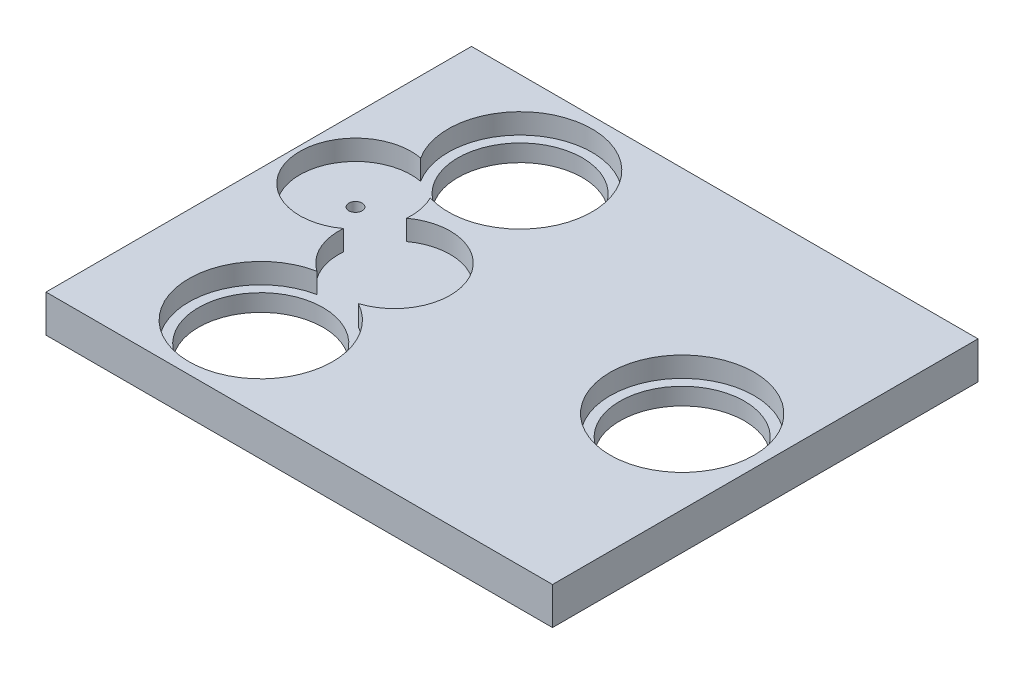
SolidWorks part; units mm, degrees
ref_plane "Front" through (0, 0, 0) normal (0, 0, 1) x (1, 0, 0)
ref_plane "Top" through (0, 0, 0) normal (0, 1, 0) x (1, 0, 0)
ref_plane "Right" through (0, 0, 0) normal (1, 0, 0) x (0, 0, -1)
sketch "Sketch1" plane through (0, 0, 0) normal (0, 1, 0) x (1, 0, 0)
  line L1 (-62.5, -52.5) -> (62.5, -52.5)
  line L2 (-62.5, -52.5) -> (-62.5, 52.5)
  line L3 (-62.5, 52.5) -> (62.5, 52.5)
  line L4 (62.5, -52.5) -> (62.5, 52.5)
  line L5 (-62.5, -52.5) -> (62.5, 52.5) construction
  line L6 (-62.5, 52.5) -> (62.5, -52.5) construction
  point P0 (0, 0)
  dimension "D1" = 125
  dimension "D2" = 105
extrude "Test_Base_Postion" add sketch "Sketch1" along normal blind 9.215
sketch "Thumb_Position" plane through (0, 9.215, 0) normal (0, 1, 0) x (1, 0, 0)
  line L0 (62.5, -52.5) -> (62.5, 52.5) construction
  line L1 (49, -12) -> (17, -12)
  line L2 (49, -12) -> (49, 43)
  line L3 (49, 43) -> (17, 43)
  line L4 (17, -12) -> (17, 43)
  line L5 (33, 43) -> (33, -12) construction
  line L6 (51, -12) -> (15, -12)
  line L7 (51, -12) -> (51, 12)
  line L8 (51, 12) -> (15, 12)
  line L9 (15, -12) -> (15, 12)
  line L10 (33, 12) -> (33, -12) construction
  line L12 (51, 0) -> (15, 0) construction
  circle A1 centre (42, 0) radius 9
  circle A2 centre (42, 0) radius 17.75 construction
  dimension "D6" = 18
  dimension "D7" = 20.5
  dimension "D5" = 35.5
  dimension "D1" = 55
  dimension "D2" = 32
  dimension "D3" = 36
  dimension "D4" = 24
sketch "Finger_Gears_Position" plane through (0, 0, 0) normal (0, -1, 0) x (1, 0, 0)
  line L0 (-30, 32) -> (-30, 49.5) construction
  line L1 (-30, 32) -> (-47.5, 32) construction
  line L2 (-30, -32) -> (-30, -49.5) construction
  line L3 (-30, -32) -> (-47.5, -32) construction
  line L4 (-62.5, -52.5) -> (-62.5, 52.5) construction
  line L5 (-62.5, 52.5) -> (62.5, 52.5) construction
  line L8 (62.5, -52.5) -> (-62.5, -52.5) construction
  line L9 (-62.5, 0) -> (62.5, 0) construction
  line L10 (62.5, 52.5) -> (62.5, -52.5) construction
  line L13 (-30, -32) -> (-43, -32) construction
  line L15 (-43, -48) -> (12, -48) construction
  line L16 (-43, -48) -> (-43, -16) construction
  line L17 (-43, -16) -> (12, -16) construction
  line L18 (12, -48) -> (12, -16) construction
  line L20 (-30, 32) -> (-43, 32) construction
  line L21 (12, -32) -> (-23, -32) construction
  line L22 (-43, 16) -> (12, 16) construction
  line L23 (-43, 16) -> (-43, 48) construction
  line L24 (-43, 48) -> (12, 48) construction
  line L25 (12, 16) -> (12, 48) construction
  line L26 (12, 32) -> (-23, 32) construction
  line L27 (-23, -32) -> (-23, 32) construction
  circle A0 centre (-30, 32) radius 17.5 construction
  circle A1 centre (-30, -32) radius 17.5 construction
  dimension "D1" = 35
  dimension "D2" = 15
  dimension "D3" = 3
  dimension "D4" = 3
  dimension "D5" = 13
  dimension "D6" = 55
  dimension "D7" = 32
  dimension "D8" = 13
  dimension "D9" = 55
  dimension "D10" = 32
  dimension "D11" = 35
  dimension "D12" = 35
sketch "Fingers_Position" plane through (0, 9.215, 0) normal (0, 1, 0) x (1, 0, 0)
  line L0 (12, 32) -> (-23, 32) construction
  line L1 (12, 16) -> (-43, 16)
  line L2 (12, 16) -> (12, 48)
  line L3 (12, 48) -> (-43, 48)
  line L4 (-43, 16) -> (-43, 48)
  line L5 (12, -48) -> (-43, -48)
  line L6 (12, -48) -> (12, -16)
  line L7 (12, -16) -> (-43, -16)
  line L8 (-43, -48) -> (-43, -16)
  line L9 (-23, 32) -> (-23, -32) construction
  line L10 (-23, -32) -> (12, -32) construction
sketch "Thumb_Knuckle_Mount_Position" plane through (0, 0, 0) normal (0, -1, 0) x (1, 0, 0)
  circle A0 centre (42, 0) radius 17.75
  dimension "D1" = 35.5
sketch "Gears_Position" plane through (0, 0, 0) normal (0, -1, 0) x (-1, 0, 0)
  line L0 (30, 32) -> (30, 13.5) construction
  line L1 (30, 32) -> (30.5905, 16.5113) construction
  line L2 (30.7851, 15.5187) -> (29.2149, 15.5187) construction
  line L3 (31.4977, 13.5607) -> (30, 17.6757) construction
  line L4 (28.2415, 13.5838) -> (30, 32) construction
  line L5 (29.2149, 15.5187) -> (27.6518, 15.6679) construction
  line L6 (30, -32) -> (30, -50.5) construction
  line L7 (30.7851, -48.4813) -> (29.2149, -48.4813) construction
  line L8 (30.5905, -47.4887) -> (30, -32) construction
  line L9 (31.4977, -50.4393) -> (30, -46.3243) construction
  line L10 (30, -32) -> (28.2415, -50.4162) construction
  line L11 (29.2149, -48.4813) -> (27.6518, -48.3321) construction
  line L12 (47.5, 8.8753) -> (47.5, -5.6247) construction
  line L13 (47.5, 8.8753) -> (48.0842, -2.6098) construction
  line L14 (48.2849, -3.6) -> (46.7151, -3.6) construction
  line L15 (48.9937, -5.5475) -> (47.5, -1.4436) construction
  line L16 (47.5, 8.8753) -> (45.6827, -5.5103) construction
  line L17 (46.7151, -3.6) -> (45.1577, -3.4033) construction
  line L18 (26.4633, -15.7991) -> (24.8935, -15.7991) construction
  line L19 (25.6784, -3.3238) -> (23.8611, -17.7095) construction
  line L20 (24.8935, -15.7991) -> (23.3362, -15.6024) construction
  line L21 (25.6784, -3.3238) -> (25.6784, -17.8238) construction
  line L22 (25.6784, -3.3238) -> (26.2626, -14.809) construction
  line L23 (27.1722, -17.7467) -> (25.6784, -13.6427) construction
  line L24 (-0.062, 11.1823) -> (33.5, -16.1231) construction
  line L25 (35.7758, 7.7687) -> (-2.3378, -12.7095) construction
  line L26 (-0.062, 11.1823) -> (35.7758, 7.7687) construction
  line L27 (-0.062, 11.1823) -> (-2.3378, -12.7095) construction
  line L28 (-2.3378, -12.7095) -> (33.5, -16.1231) construction
  line L29 (35.7758, 7.7687) -> (33.5, -16.1231) construction
  line L30 (16.719, -2.4704) -> (34.6379, -4.1772) construction
  line L31 (62.5, 52.5) -> (62.5, -52.5) construction
  circle A0 centre (30, -32) radius 17.5 construction
  circle A1 centre (30, 32) radius 17.5 construction
  circle A2 centre (30, 32) radius 16.5
  circle A3 centre (30, 32) radius 15.5 construction
  circle A4 centre (30, 32) radius 18.5 construction
  arc A5 (32.4899, 13.6683) -> (30.5905, 16.5113) centre (33.854, 16.6357) cw
  arc A6 (27.5101, 13.6683) -> (29.4095, 16.5113) centre (26.146, 16.6357) ccw
  arc A7 (32.4899, -50.3317) -> (30.5905, -47.4887) centre (33.854, -47.3643) cw
  arc A8 (27.5101, -50.3317) -> (29.4095, -47.4887) centre (26.146, -47.3643) ccw
  circle A9 centre (30, -32) radius 16.5
  circle A10 centre (30, -32) radius 18.5 construction
  circle A11 centre (30, -32) radius 15.5 construction
  arc A12 (28.9757, -50.4716) -> (27.6486, -47.3206) centre (30.8766, -47.816) cw
  arc A13 (24.0858, -49.5292) -> (26.4889, -47.0971) centre (23.3079, -46.3573) ccw
  arc A14 (25.4984, -49.944) -> (24.7916, -46.5987) centre (27.8676, -47.6961) cw
  arc A15 (20.8752, -48.0931) -> (23.6952, -46.1598) centre (20.7117, -44.8314) ccw
  arc A16 (22.1838, -48.7678) -> (22.1229, -45.3492) centre (24.9356, -47.0089) cw
  arc A17 (17.9945, -46.0754) -> (21.1294, -44.7107) centre (18.4512, -42.8417) ccw
  arc A18 (19.1518, -46.9855) -> (19.7389, -43.6172) centre (22.1867, -45.7792) cw
  arc A19 (15.5476, -43.549) -> (18.8842, -42.8022) centre (16.6081, -40.4601) ccw
  arc A20 (16.5118, -44.6617) -> (17.7258, -41.4654) centre (19.7201, -44.0516) cw
  arc A21 (13.6232, -40.6052) -> (17.0407, -40.5033) centre (15.2491, -37.7728) ccw
  arc A22 (14.3593, -41.8802) -> (16.1562, -38.9714) centre (17.6251, -41.8883) cw
  arc A23 (12.2906, -37.3503) -> (15.6656, -37.8971) centre (14.4231, -34.8769) ccw
  arc A24 (12.7721, -38.7416) -> (15.0871, -36.2255) centre (15.9774, -39.3676) cw
  arc A25 (11.598, -33.9021) -> (14.8086, -35.0777) centre (14.1602, -31.8769) ccw
  arc A26 (11.8076, -35.3594) -> (14.5569, -33.3268) centre (14.8365, -36.5807) cw
  arc A27 (11.5706, -30.3851) -> (14.5007, -32.1471) centre (14.4697, -28.8814) ccw
  arc A28 (11.5006, -31.8557) -> (14.5849, -30.3802) centre (14.2436, -33.6282) cw
  arc A29 (12.2093, -26.9265) -> (14.7529, -29.2112) centre (15.3405, -25.9987) ccw
  arc A30 (11.8622, -28.3573) -> (15.17, -27.4922) centre (14.2202, -30.6169) cw
  arc A31 (13.4909, -23.6513) -> (15.5563, -26.3761) centre (16.7412, -23.3328) ccw
  arc A32 (12.8793, -24.9905) -> (16.2911, -24.767) centre (14.7671, -27.6555) cw
  arc A33 (15.3693, -20.6778) -> (16.8816, -23.7442) centre (18.6211, -20.9802) ccw
  arc A34 (14.5153, -21.8771) -> (17.9077, -22.3033) centre (15.8646, -24.8512) cw
  arc A35 (17.7764, -18.1135) -> (18.6811, -21.4107) centre (20.9122, -19.0259) ccw
  arc A36 (16.7109, -19.1295) -> (19.9613, -20.1901) centre (17.473, -22.3052) cw
  arc A37 (20.6253, -16.0511) -> (20.8897, -19.46) centre (23.5318, -17.5404) ccw
  arc A38 (19.3868, -16.8471) -> (22.3778, -18.5036) centre (19.5341, -20.1096) cw
  arc A39 (23.8131, -14.5652) -> (23.4275, -17.9625) centre (26.3852, -16.5776) ccw
  arc A40 (22.4463, -15.1124) -> (25.0697, -17.305) centre (21.9735, -18.3438) cw
  arc A41 (27.2245, -13.7094) -> (26.2029, -16.9723) centre (29.3693, -16.1722) ccw
  arc A42 (25.7788, -13.988) -> (27.9399, -16.6375) centre (24.703, -17.0716) cw
  arc A43 (30.7361, -13.5147) -> (29.1155, -16.5253) centre (32.3761, -16.3389) ccw
  arc A44 (29.2639, -13.5147) -> (30.8845, -16.5253) centre (27.6239, -16.3389) cw
  arc A45 (34.2212, -13.988) -> (32.0601, -16.6375) centre (35.297, -17.0716) ccw
  arc A46 (32.7755, -13.7094) -> (33.7971, -16.9723) centre (30.6307, -16.1722) cw
  arc A47 (37.5537, -15.1124) -> (34.9303, -17.305) centre (38.0265, -18.3438) ccw
  arc A48 (36.1869, -14.5652) -> (36.5725, -17.9625) centre (33.6148, -16.5776) cw
  arc A49 (40.6132, -16.8471) -> (37.6222, -18.5036) centre (40.4659, -20.1096) ccw
  arc A50 (39.3747, -16.0511) -> (39.1103, -19.46) centre (36.4682, -17.5404) cw
  arc A51 (43.2891, -19.1295) -> (40.0387, -20.1901) centre (42.527, -22.3052) ccw
  arc A52 (42.2236, -18.1135) -> (41.3189, -21.4107) centre (39.0878, -19.0259) cw
  arc A53 (45.4847, -21.8771) -> (42.0923, -22.3033) centre (44.1354, -24.8512) ccw
  arc A54 (44.6307, -20.6778) -> (43.1184, -23.7442) centre (41.3789, -20.9802) cw
  arc A55 (47.1207, -24.9905) -> (43.7089, -24.767) centre (45.2329, -27.6555) ccw
  arc A56 (46.5091, -23.6513) -> (44.4437, -26.3761) centre (43.2588, -23.3328) cw
  arc A57 (48.1378, -28.3573) -> (44.83, -27.4922) centre (45.7798, -30.6169) ccw
  arc A58 (47.7907, -26.9265) -> (45.2471, -29.2112) centre (44.6595, -25.9987) cw
  arc A59 (48.4994, -31.8557) -> (45.4151, -30.3802) centre (45.7564, -33.6282) ccw
  arc A60 (48.4294, -30.3851) -> (45.4993, -32.1471) centre (45.5303, -28.8814) cw
  arc A61 (48.1924, -35.3594) -> (45.4431, -33.3268) centre (45.1635, -36.5807) ccw
  arc A62 (48.402, -33.9021) -> (45.1914, -35.0777) centre (45.8398, -31.8769) cw
  arc A63 (47.2279, -38.7416) -> (44.9129, -36.2255) centre (44.0226, -39.3676) ccw
  arc A64 (47.7094, -37.3503) -> (44.3344, -37.8971) centre (45.5769, -34.8769) cw
  arc A65 (45.6407, -41.8802) -> (43.8438, -38.9714) centre (42.3749, -41.8883) ccw
  arc A66 (46.3768, -40.6052) -> (42.9593, -40.5033) centre (44.7509, -37.7728) cw
  arc A67 (43.4882, -44.6617) -> (42.2742, -41.4654) centre (40.2799, -44.0516) ccw
  arc A68 (44.4524, -43.549) -> (41.1158, -42.8022) centre (43.3919, -40.4601) cw
  arc A69 (40.8482, -46.9855) -> (40.2611, -43.6172) centre (37.8133, -45.7792) ccw
  arc A70 (42.0055, -46.0754) -> (38.8706, -44.7107) centre (41.5488, -42.8417) cw
  arc A71 (37.8162, -48.7678) -> (37.8771, -45.3492) centre (35.0644, -47.0089) ccw
  arc A72 (39.1248, -48.0931) -> (36.3048, -46.1598) centre (39.2883, -44.8314) cw
  arc A73 (34.5016, -49.944) -> (35.2084, -46.5987) centre (32.1324, -47.6961) ccw
  arc A74 (35.9142, -49.5292) -> (33.5111, -47.0971) centre (36.6921, -46.3573) cw
  arc A75 (31.0243, -50.4716) -> (32.3514, -47.3206) centre (29.1234, -47.816) ccw
  arc A76 (28.9757, 13.5284) -> (27.6486, 16.6794) centre (30.8766, 16.184) cw
  arc A77 (24.0858, 14.4708) -> (26.4889, 16.9029) centre (23.3079, 17.6427) ccw
  arc A78 (25.4984, 14.056) -> (24.7916, 17.4013) centre (27.8676, 16.3039) cw
  arc A79 (20.8752, 15.9069) -> (23.6952, 17.8402) centre (20.7117, 19.1686) ccw
  arc A80 (22.1838, 15.2322) -> (22.1229, 18.6508) centre (24.9356, 16.9911) cw
  arc A81 (17.9945, 17.9246) -> (21.1294, 19.2893) centre (18.4512, 21.1583) ccw
  arc A82 (19.1518, 17.0145) -> (19.7389, 20.3828) centre (22.1867, 18.2208) cw
  arc A83 (15.5476, 20.451) -> (18.8842, 21.1978) centre (16.6081, 23.5399) ccw
  arc A84 (16.5118, 19.3383) -> (17.7258, 22.5346) centre (19.7201, 19.9484) cw
  arc A85 (13.6232, 23.3948) -> (17.0407, 23.4967) centre (15.2491, 26.2272) ccw
  arc A86 (14.3593, 22.1198) -> (16.1562, 25.0286) centre (17.6251, 22.1117) cw
  arc A87 (12.2906, 26.6497) -> (15.6656, 26.1029) centre (14.4231, 29.1231) ccw
  arc A88 (12.7721, 25.2584) -> (15.0871, 27.7745) centre (15.9774, 24.6324) cw
  arc A89 (11.598, 30.0979) -> (14.8086, 28.9223) centre (14.1602, 32.1231) ccw
  arc A90 (11.8076, 28.6406) -> (14.5569, 30.6732) centre (14.8365, 27.4193) cw
  arc A91 (11.5706, 33.6149) -> (14.5007, 31.8529) centre (14.4697, 35.1186) ccw
  arc A92 (11.5006, 32.1443) -> (14.5849, 33.6198) centre (14.2436, 30.3718) cw
  arc A93 (12.2093, 37.0735) -> (14.7529, 34.7888) centre (15.3405, 38.0013) ccw
  arc A94 (11.8622, 35.6427) -> (15.17, 36.5078) centre (14.2202, 33.3831) cw
  arc A95 (13.4909, 40.3487) -> (15.5563, 37.6239) centre (16.7412, 40.6672) ccw
  arc A96 (12.8793, 39.0095) -> (16.2911, 39.233) centre (14.7671, 36.3445) cw
  arc A97 (15.3693, 43.3222) -> (16.8816, 40.2558) centre (18.6211, 43.0198) ccw
  arc A98 (14.5153, 42.1229) -> (17.9077, 41.6967) centre (15.8646, 39.1488) cw
  arc A99 (17.7764, 45.8865) -> (18.6811, 42.5893) centre (20.9122, 44.9741) ccw
  arc A100 (16.7109, 44.8705) -> (19.9613, 43.8099) centre (17.473, 41.6948) cw
  arc A101 (20.6253, 47.9489) -> (20.8897, 44.54) centre (23.5318, 46.4596) ccw
  arc A102 (19.3868, 47.1529) -> (22.3778, 45.4964) centre (19.5341, 43.8904) cw
  arc A103 (23.8131, 49.4348) -> (23.4275, 46.0375) centre (26.3852, 47.4224) ccw
  arc A104 (22.4463, 48.8876) -> (25.0697, 46.695) centre (21.9735, 45.6562) cw
  arc A105 (27.2245, 50.2906) -> (26.2029, 47.0277) centre (29.3693, 47.8278) ccw
  arc A106 (25.7788, 50.012) -> (27.9399, 47.3625) centre (24.703, 46.9284) cw
  arc A107 (30.7361, 50.4853) -> (29.1155, 47.4747) centre (32.3761, 47.6611) ccw
  arc A108 (29.2639, 50.4853) -> (30.8845, 47.4747) centre (27.6239, 47.6611) cw
  arc A109 (34.2212, 50.012) -> (32.0601, 47.3625) centre (35.297, 46.9284) ccw
  arc A110 (32.7755, 50.2906) -> (33.7971, 47.0277) centre (30.6307, 47.8278) cw
  arc A111 (37.5537, 48.8876) -> (34.9303, 46.695) centre (38.0265, 45.6562) ccw
  arc A112 (36.1869, 49.4348) -> (36.5725, 46.0375) centre (33.6148, 47.4224) cw
  arc A113 (40.6132, 47.1529) -> (37.6222, 45.4964) centre (40.4659, 43.8904) ccw
  arc A114 (39.3747, 47.9489) -> (39.1103, 44.54) centre (36.4682, 46.4596) cw
  arc A115 (43.2891, 44.8705) -> (40.0387, 43.8099) centre (42.527, 41.6948) ccw
  arc A116 (42.2236, 45.8865) -> (41.3189, 42.5893) centre (39.0878, 44.9741) cw
  arc A117 (45.4847, 42.1229) -> (42.0923, 41.6967) centre (44.1354, 39.1488) ccw
  arc A118 (44.6307, 43.3222) -> (43.1184, 40.2558) centre (41.3789, 43.0198) cw
  arc A119 (47.1207, 39.0095) -> (43.7089, 39.233) centre (45.2329, 36.3445) ccw
  arc A120 (46.5091, 40.3487) -> (44.4437, 37.6239) centre (43.2588, 40.6672) cw
  arc A121 (48.1378, 35.6427) -> (44.83, 36.5078) centre (45.7798, 33.3831) ccw
  arc A122 (47.7907, 37.0735) -> (45.2471, 34.7888) centre (44.6595, 38.0013) cw
  arc A123 (48.4994, 32.1443) -> (45.4151, 33.6198) centre (45.7564, 30.3718) ccw
  arc A124 (48.4294, 33.6149) -> (45.4993, 31.8529) centre (45.5303, 35.1186) cw
  arc A125 (48.1924, 28.6406) -> (45.4431, 30.6732) centre (45.1635, 27.4193) ccw
  arc A126 (48.402, 30.0979) -> (45.1914, 28.9223) centre (45.8398, 32.1231) cw
  arc A127 (47.2279, 25.2584) -> (44.9129, 27.7745) centre (44.0226, 24.6324) ccw
  arc A128 (47.7094, 26.6497) -> (44.3344, 26.1029) centre (45.5769, 29.1231) cw
  arc A129 (45.6407, 22.1198) -> (43.8438, 25.0286) centre (42.3749, 22.1117) ccw
  arc A130 (46.3768, 23.3948) -> (42.9593, 23.4967) centre (44.7509, 26.2272) cw
  arc A131 (43.4882, 19.3383) -> (42.2742, 22.5346) centre (40.2799, 19.9484) ccw
  arc A132 (44.4524, 20.451) -> (41.1158, 21.1978) centre (43.3919, 23.5399) cw
  arc A133 (40.8482, 17.0145) -> (40.2611, 20.3828) centre (37.8133, 18.2208) ccw
  arc A134 (42.0055, 17.9246) -> (38.8706, 19.2893) centre (41.5488, 21.1583) cw
  arc A135 (37.8162, 15.2322) -> (37.8771, 18.6508) centre (35.0644, 16.9911) ccw
  arc A136 (39.1248, 15.9069) -> (36.3048, 17.8402) centre (39.2883, 19.1686) cw
  arc A137 (34.5016, 14.056) -> (35.2084, 17.4013) centre (32.1324, 16.3039) ccw
  arc A138 (35.9142, 14.4708) -> (33.5111, 16.9029) centre (36.6921, 17.6427) cw
  arc A139 (31.0243, 13.5284) -> (32.3514, 16.6794) centre (29.1234, 16.184) ccw
  circle A140 centre (47.5, 8.8753) radius 11.5 construction
  circle A141 centre (47.5, 8.8753) radius 12.5
  circle A142 centre (47.5, 8.8753) radius 13.5 construction
  circle A143 centre (47.5, 8.8753) radius 14.5 construction
  arc A144 (49.8668, -5.4302) -> (48.0842, -2.6098) centre (51.48, -2.4371) cw
  arc A145 (45.1332, -5.4302) -> (46.9158, -2.6098) centre (43.52, -2.4371) ccw
  arc A146 (23.3116, -17.6293) -> (25.0942, -14.809) centre (21.6985, -14.6362) ccw
  circle A147 centre (25.6784, -3.3238) radius 11.5 construction
  circle A148 centre (25.6784, -3.3238) radius 12.5
  arc A149 (28.0453, -17.6293) -> (26.2626, -14.809) centre (29.6584, -14.6362) cw
  circle A150 centre (25.6784, -3.3238) radius 13.5 construction
  circle A151 centre (25.6784, -3.3238) radius 14.5 construction
  arc A152 (46.2348, -5.5694) -> (45.2096, -2.3943) centre (48.5416, -3.0715) cw
  arc A153 (41.6499, -4.3922) -> (44.0779, -2.1037) centre (40.8318, -1.0919) ccw
  arc A154 (42.6823, -4.8009) -> (42.4789, -1.4706) centre (45.5379, -2.9552) cw
  arc A155 (38.5342, -2.5205) -> (41.455, -0.9077) centre (38.5625, 0.8796) ccw
  arc A156 (39.4325, -3.1731) -> (40.0638, 0.1031) centre (42.6574, -2.0955) cw
  arc A157 (35.9819, 0.0673) -> (39.212, 0.9029) centre (36.8548, 3.3534) ccw
  arc A158 (36.6896, -0.7883) -> (38.1158, 2.228) centre (40.0812, -0.5466) cw
  arc A159 (34.1532, 3.2084) -> (37.4897, 3.2146) centre (35.816, 6.1742) ccw
  arc A160 (34.626, 2.2037) -> (36.7575, 4.7706) centre (37.9711, 1.5944) cw
  arc A161 (33.1632, 6.7057) -> (36.3964, 5.8819) centre (35.5114, 9.1648) ccw
  arc A162 (33.3713, 5.6149) -> (36.0742, 7.5711) centre (36.4598, 4.1929) cw
  arc A163 (33.0741, 10.3392) -> (36.0008, 8.7372) centre (35.96, 12.1371) ccw
  arc A164 (33.0044, 9.231) -> (36.1088, 10.4536) centre (35.6422, 7.0856) cw
  arc A165 (33.8914, 13.8808) -> (36.3278, 11.6013) centre (37.1337, 14.9045) ccw
  arc A166 (33.5482, 12.8248) -> (36.8592, 13.2369) centre (35.5696, 10.0908) cw
  arc A167 (35.5637, 17.1079) -> (37.3567, 14.2941) centre (38.9588, 17.2931) ccw
  arc A168 (34.9687, 16.1704) -> (38.2781, 15.7461) centre (36.2467, 13.0195) cw
  arc A169 (37.9861, 19.8177) -> (39.0229, 16.6464) centre (41.3206, 19.1528) ccw
  arc A170 (37.1766, 19.0576) -> (40.2766, 17.8236) centre (37.6309, 15.6879) cw
  arc A171 (41.0062, 21.8399) -> (41.2218, 18.5104) centre (44.0706, 20.3666) ccw
  arc A172 (40.0332, 21.305) -> (42.7288, 19.3389) centre (39.6351, 17.9282) cw
  arc A173 (44.4344, 23.0476) -> (43.8152, 19.769) centre (47.0361, 20.8585) ccw
  arc A174 (43.3589, 22.7714) -> (45.4809, 20.1967) centre (42.1336, 19.5997) cw
  arc A175 (48.0552, 23.3647) -> (46.6401, 20.3431) centre (50.0308, 20.5974) ccw
  arc A176 (46.9448, 23.3647) -> (48.3599, 20.3431) centre (44.9692, 20.5974) cw
  arc A177 (51.6411, 22.7714) -> (49.5191, 20.1967) centre (52.8664, 19.5997) ccw
  arc A178 (50.5656, 23.0476) -> (51.1848, 19.769) centre (47.9639, 20.8585) cw
  arc A179 (54.9668, 21.305) -> (52.2712, 19.3389) centre (55.3649, 17.9282) ccw
  arc A180 (53.9938, 21.8399) -> (53.7782, 18.5104) centre (50.9294, 20.3666) cw
  arc A181 (57.8234, 19.0576) -> (54.7234, 17.8236) centre (57.3691, 15.6879) ccw
  arc A182 (57.0139, 19.8177) -> (55.9771, 16.6464) centre (53.6794, 19.1528) cw
  arc A183 (60.0313, 16.1704) -> (56.7219, 15.7461) centre (58.7533, 13.0195) ccw
  arc A184 (59.4363, 17.1079) -> (57.6433, 14.2941) centre (56.0412, 17.2931) cw
  arc A185 (61.4518, 12.8248) -> (58.1408, 13.2369) centre (59.4304, 10.0908) ccw
  arc A186 (61.1086, 13.8808) -> (58.6722, 11.6013) centre (57.8663, 14.9045) cw
  arc A187 (61.9956, 9.231) -> (58.8912, 10.4536) centre (59.3578, 7.0856) ccw
  arc A188 (61.9259, 10.3392) -> (58.9992, 8.7372) centre (59.04, 12.1371) cw
  arc A189 (61.6287, 5.6149) -> (58.9258, 7.5711) centre (58.5402, 4.1929) ccw
  arc A190 (61.8368, 6.7057) -> (58.6036, 5.8819) centre (59.4886, 9.1648) cw
  arc A191 (60.374, 2.2037) -> (58.2425, 4.7706) centre (57.0289, 1.5944) ccw
  arc A192 (60.8468, 3.2084) -> (57.5103, 3.2146) centre (59.184, 6.1742) cw
  arc A193 (58.3104, -0.7883) -> (56.8842, 2.228) centre (54.9188, -0.5466) ccw
  arc A194 (59.0181, 0.0673) -> (55.788, 0.9029) centre (58.1452, 3.3534) cw
  arc A195 (55.5675, -3.1731) -> (54.9362, 0.1031) centre (52.3426, -2.0955) ccw
  arc A196 (56.4658, -2.5205) -> (53.545, -0.9077) centre (56.4375, 0.8796) cw
  arc A197 (52.3177, -4.8009) -> (52.5211, -1.4706) centre (49.4621, -2.9552) ccw
  arc A198 (53.3501, -4.3922) -> (50.9221, -2.1037) centre (54.1682, -1.0919) cw
  arc A199 (48.7652, -5.5694) -> (49.7904, -2.3943) centre (46.4584, -3.0715) ccw
  arc A200 (19.8283, -16.5913) -> (22.2563, -14.3028) centre (19.0102, -13.291) ccw
  arc A201 (24.4133, -17.7685) -> (23.3881, -14.5934) centre (26.7201, -15.2706) cw
  arc A202 (16.7126, -14.7196) -> (19.6335, -13.1069) centre (16.741, -11.3196) ccw
  arc A203 (20.8608, -17.0001) -> (20.6574, -13.6698) centre (23.7163, -15.1543) cw
  arc A204 (14.1603, -12.1319) -> (17.3904, -11.2962) centre (15.0333, -8.8457) ccw
  arc A205 (17.611, -15.3723) -> (18.2422, -12.096) centre (20.8358, -14.2947) cw
  arc A206 (12.3317, -8.9907) -> (15.6682, -8.9846) centre (13.9945, -6.0249) ccw
  arc A207 (14.8681, -12.9875) -> (16.2942, -9.9711) centre (18.2596, -12.7457) cw
  arc A208 (11.3417, -5.4935) -> (14.5749, -6.3173) centre (13.6898, -3.0344) ccw
  arc A209 (12.8045, -9.9954) -> (14.9359, -7.4285) centre (16.1496, -10.6047) cw
  arc A210 (11.2525, -1.8599) -> (14.1793, -3.4619) centre (14.1384, -0.062) ccw
  arc A211 (11.5497, -6.5842) -> (14.2526, -4.628) centre (14.6382, -8.0062) cw
  arc A212 (12.0698, 1.6817) -> (14.5062, -0.5978) centre (15.3122, 2.7054) ccw
  arc A213 (11.1828, -2.9681) -> (14.2872, -1.7456) centre (13.8206, -5.1135) cw
  arc A214 (13.7421, 4.9088) -> (15.5351, 2.0949) centre (17.1372, 5.094) ccw
  arc A215 (11.7267, 0.6256) -> (15.0376, 1.0377) centre (13.7481, -2.1084) cw
  arc A216 (16.1645, 7.6185) -> (17.2014, 4.4473) centre (19.499, 6.9536) ccw
  arc A217 (13.1472, 3.9712) -> (16.4566, 3.547) centre (14.4251, 0.8204) cw
  arc A218 (19.1847, 9.6408) -> (19.4003, 6.3113) centre (22.249, 8.1675) ccw
  arc A219 (15.3551, 6.8584) -> (18.455, 5.6245) centre (15.8093, 3.4888) cw
  arc A220 (22.6128, 10.8484) -> (21.9937, 7.5699) centre (25.2145, 8.6593) ccw
  arc A221 (18.2116, 9.1059) -> (20.9073, 7.1398) centre (17.8136, 5.7291) cw
  arc A222 (26.2336, 11.1656) -> (24.8186, 8.144) centre (28.2092, 8.3982) ccw
  arc A223 (21.5373, 10.5723) -> (23.6593, 7.9976) centre (20.312, 7.4006) cw
  arc A224 (29.8195, 10.5723) -> (27.6975, 7.9976) centre (31.0448, 7.4006) ccw
  arc A225 (25.1232, 11.1656) -> (26.5383, 8.144) centre (23.1477, 8.3982) cw
  arc A226 (33.1453, 9.1059) -> (30.4496, 7.1398) centre (33.5433, 5.7291) ccw
  arc A227 (28.744, 10.8484) -> (29.3632, 7.5699) centre (26.1423, 8.6593) cw
  arc A228 (36.0018, 6.8584) -> (32.9019, 5.6245) centre (35.5476, 3.4888) ccw
  arc A229 (32.1722, 9.6408) -> (31.9566, 6.3113) centre (29.1078, 8.1675) cw
  arc A230 (38.2097, 3.9712) -> (34.9003, 3.547) centre (36.9317, 0.8204) ccw
  arc A231 (35.1924, 7.6185) -> (34.1555, 4.4473) centre (31.8579, 6.9536) cw
  arc A232 (39.6302, 0.6256) -> (36.3193, 1.0377) centre (37.6088, -2.1084) ccw
  arc A233 (37.6147, 4.9088) -> (35.8218, 2.0949) centre (34.2196, 5.094) cw
  arc A234 (40.1741, -2.9681) -> (37.0696, -1.7456) centre (37.5362, -5.1135) ccw
  arc A235 (39.2871, 1.6817) -> (36.8507, -0.5978) centre (36.0447, 2.7054) cw
  arc A236 (39.8071, -6.5842) -> (37.1042, -4.628) centre (36.7186, -8.0062) ccw
  arc A237 (40.1043, -1.8599) -> (37.1776, -3.4619) centre (37.2184, -0.062) cw
  arc A238 (38.5524, -9.9954) -> (36.4209, -7.4285) centre (35.2073, -10.6047) ccw
  arc A239 (40.0152, -5.4935) -> (36.782, -6.3173) centre (37.6671, -3.0344) cw
  arc A240 (36.4888, -12.9875) -> (35.0626, -9.9711) centre (33.0972, -12.7457) ccw
  arc A241 (39.0252, -8.9907) -> (35.6887, -8.9846) centre (37.3624, -6.0249) cw
  arc A242 (33.7459, -15.3723) -> (33.1147, -12.096) centre (30.521, -14.2947) ccw
  arc A243 (37.1966, -12.1319) -> (33.9664, -11.2962) centre (36.3236, -8.8457) cw
  arc A244 (30.4961, -17.0001) -> (30.6995, -13.6698) centre (27.6406, -15.1543) ccw
  arc A245 (34.6442, -14.7196) -> (31.7234, -13.1069) centre (34.6159, -11.3196) cw
  arc A246 (26.9436, -17.7685) -> (27.9688, -14.5934) centre (24.6368, -15.2706) ccw
  arc A247 (31.5285, -16.5913) -> (29.1005, -14.3028) centre (32.3466, -13.291) cw
  point P233 (30, -32)
  point P426 (30, 32)
  point P461 (16.719, -2.4704)
  point P607 (47.5, 8.8753)
  point P608 (25.6784, -3.3238)
  point P753 (25.6784, -3.3238)
  dimension "D1" = 35
  dimension "D2" = 31
  dimension "D3" = 33
  dimension "D4" = 37
  dimension "D7" = 37
  dimension "D8" = 33
  dimension "D9" = 31
  dimension "D14" = 23
  dimension "D15" = 25
  dimension "D16" = 27
  dimension "D17" = 29
  dimension "D20" = 23
  dimension "D21" = 25
  dimension "D22" = 27
  dimension "D23" = 29
  dimension "D5" = 20
  dimension "D6" = 5.455
  dimension "D10" = 20
  dimension "D11" = 5.455
  dimension "D18" = 20
  dimension "D19" = 7.2
  dimension "D24" = 20
  dimension "D25" = 7.2
  dimension "D28" = 36
  dimension "D29" = 24
  dimension "D30" = 29
  dimension "D31" = 15
  dimension "D12" = 33
  dimension "D13" = 33
  dimension "D26" = 25
  dimension "D27" = 25
sketch "XL320_Position" plane through (0, 9.215, 0) normal (0, 1, 0) x (1, 0, 0)
  line L0 (0.062, 11.1823) -> (2.3378, -12.7095)
  line L1 (2.3378, -12.7095) -> (-33.5, -16.1231)
  line L2 (-33.5, -16.1231) -> (-35.7758, 7.7687)
  line L3 (-35.7758, 7.7687) -> (0.062, 11.1823)
sketch "Sketch7" plane through (0, 0, 0) normal (0, -1, 0) x (1, 0, 0)
  circle A0 centre (42, 0) radius 17.75
  dimension "D1" = 35.5
extrude "Thumb_Knuckle_Mount" cut sketch "Sketch7" against normal up to surface (9.215 mm away) from offset 4.215 up to face at (0, 9.215, 0) offset against normal yes
sketch "Sketch8" plane through (0, 0, 0) normal (0, -1, 0) x (1, 0, 0)
  circle A0 centre (42, 0) radius 15.375
  dimension "D1" = 30.75
extrude "Thumb_Knuckle" cut sketch "Sketch8" along direction (0, -1, 0) on the side against the normal up to surface (4.215 mm away) up to face at (42, 4.215, -17.75)
sketch "Sketch10" plane through (0, 0, 0) normal (0, -1, 0) x (1, 0, 0)
  circle A0 centre (-30, 32) radius 17.75
  circle A1 centre (-25.6784, 3.3238) radius 13.75
  circle A2 centre (-47.5, -8.8753) radius 13.75
  circle A3 centre (-30, -32) radius 17.75
  dimension "D1" = 35.5
  dimension "D2" = 27.5
extrude "Gears_Position_Extrude_Cut" cut sketch "Sketch10" against normal up to surface (9.215 mm away) from offset 4.215 contours A1 A0 | A2 A1 A0 | A3 A2 A1 | A2 A3 | A0 A1 | A1 A2 | A2 A3 region at (-30.0521, 0, 32.3454) region at (-27.5364, 0, 15.6522) region at (-25.2303, 0, 3.0803) region at (-36.5892, 0, -2.7758) region at (-48.1575, 0, -8.7201) region at (-39.9764, 0, -18.817) region at (-29.7892, 0, -32.2785) up to face at (42, 9.215, -17.75) offset against normal yes
sketch "Sketch11" plane through (0, 0, 0) normal (0, -1, 0) x (1, 0, 0)
  circle A0 centre (-30, 32) radius 15.375
  circle A1 centre (-30, -32) radius 15.375
  circle A2 centre (-47.5, -8.8753) radius 1.65
  circle A3 centre (-30, 32) radius 17.75 construction
  circle A4 centre (-30, -32) radius 17.75 construction
  circle A5 centre (-47.5, -8.8753) radius 13.75 construction
  dimension "D1" = 3.3
  dimension "D2" = 30.75
extrude "Fingers_Knuckle_Mount_and_Intermediate_Through_Hole" cut sketch "Sketch11" against normal through all
equation "\"D6@Gears_Position\"=180/33"
equation "\"D11@Gears_Position\"=180/33"
equation "\"D19@Gears_Position\"=180/25"
